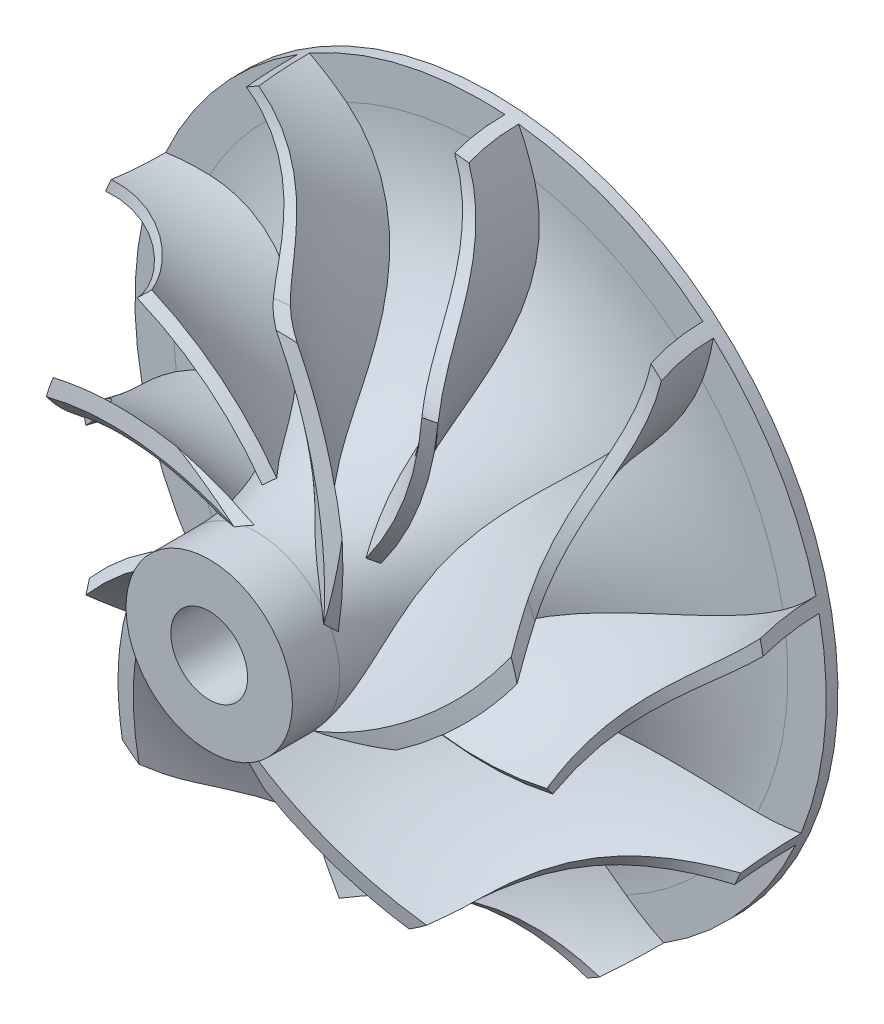
SolidWorks part; units mm, degrees
material "6061-T6 (SS)"
ref_plane "Front Plane" through (0, 0, 0) normal (0, 0, 1) x (1, 0, 0)
ref_plane "Top Plane" through (0, 0, 0) normal (0, 1, 0) x (1, 0, 0)
ref_plane "Right Plane" through (0, 0, 0) normal (1, 0, 0) x (0, 0, -1)
sketch "Sketch1" plane through (0, 0, 0) normal (1, 0, 0) x (0, 0, -1)
  line L0 (0, 0) -> (-24.5, 0) construction
  line L1 (-24.5, 3) -> (-24.5, 6.5)
  line L2 (0, 53.2891) -> (0, 0) construction
  line L3 (-24.5, 6.5) -> (-20.8, 6.5)
  line L4 (-24.5, 3) -> (0, 3)
  line L5 (0, 3) -> (0, 7)
  line L6 (-2.3876, 27) -> (-2.3876, 16.51)
  line L7 (-2.3876, 27) -> (-3.3, 27)
  line L8 (-3.3, 27) -> (-3.3, 24)
  arc A0 (-3.3, 24) -> (-20.8, 6.5) centre (-20.8, 24) cw
  arc A1 (0, 7) -> (-2.3876, 16.51) centre (17.7457, 16.51) cw
  dimension "D1" = 6
  dimension "D2" = 13
  dimension "D3" = 3.3
  dimension "D4" = 14
  dimension "D5" = 54
  dimension "D6" = 24.5
  dimension "D7" = 33.02
  dimension "D8" = 2.3876
  dimension "D9" = 48
revolve "Revolve1" add sketch "Sketch1" angle 360 about L0
sketch "Sketch2" plane through (0, 0, 0) normal (1, 0, 0) x (0, 0, -1)
  line L0 (0, 0) -> (-36.3996, 0) construction
  line L1 (-3.3, 24) -> (-3.3, -24) construction
  line L2 (-20.8, 6.5) -> (-20.8, -6.5) construction
  line L3 (-3.3, 27) -> (-3.3, -27) construction
  line L4 (-3.3, 4.5438) -> (-3.3, 5.4562)
  line L5 (-20.407, -5.2316) -> (-21.193, -4.7684)
  arc A0 (-3.3, 5) -> (-20.8, -5) centre (-3.3, -15.3125) ccw construction
  arc A1 (-3.3, 5.4562) -> (-21.193, -4.7684) centre (-3.3, -15.3125) ccw
  arc A2 (-3.3, 4.5438) -> (-20.407, -5.2316) centre (-3.3, -15.3125) ccw
  dimension "D1" = 5
  dimension "D2" = 5
  dimension "D3" = 0.4562
  dimension "D4" = 0.4562
sketch "Sketch3" plane through (0, 0, 0) normal (0, 0, 1) x (1, 0, 0)
  line L0 (0, 0) -> (40.1259, 0) construction
  line L1 (0, 0) -> (21.8435, 15.8702) construction
  arc A0 (0, 0) -> (22.9676, 22.9944) centre (0, 22.9676) ccw
  circle A2 centre (0, 0) radius 32.5 construction
  dimension "D2" = 65
  dimension "D3" = 22.9676
  dimension "D1" = 36
sweep "Sweep1" add profiles "Sketch2" path "Sketch3"
ref_axis "Axis1" through (0, 0, 24.5) along (0, 0, -1)
sketch "Sketch4" plane through (0, 0, 0) normal (1, 0, 0) x (0, 0, -1)
  line L0 (-20.8, -6.5) -> (-20.8, 6.5) construction
  line L1 (-3.3, 24) -> (-3.3, -24) construction
  line L2 (-24.5, 0) -> (0, 0) construction
  line L3 (-3.3, -5.4562) -> (-3.3, -4.5438)
  line L4 (-16.3269, 0.3268) -> (-16.9255, -0.3618)
  arc A0 (-20.8, 5) -> (-3.3, -5) centre (-3.3, 15.3125) ccw construction
  arc A1 (-16.9255, -0.3618) -> (-3.3, -5.4562) centre (-3.3, 15.3125) ccw
  arc A2 (-16.3269, 0.3268) -> (-3.3, -4.5438) centre (-3.3, 15.3125) ccw
  arc A4 (-21.193, 4.7684) -> (-3.3, -5.4562) centre (-3.3, 15.3125) ccw construction
  arc A5 (-20.407, 5.2316) -> (-3.3, -4.5438) centre (-3.3, 15.3125) ccw construction
  dimension "D1" = 5
  dimension "D2" = 5
  dimension "D5" = 41
  dimension "D3" = 0.4562
  dimension "D4" = 0.4562
sketch "Sketch5" plane through (0, 0, 0) normal (0, 0, 1) x (1, 0, 0)
  line L0 (0, 0) -> (-37.6758, 0) construction
  line L1 (-21.8435, -15.8702) -> (0, 0) construction
  arc A0 (0, 0) -> (-22.9676, -22.9944) centre (0, -22.9676) ccw
  arc A1 (17.3611, 20.6783) -> (18.1774, 19.9645) centre (0, 0) ccw construction
  circle A2 centre (0, 0) radius 32.5 construction
  dimension "D2" = 65
  dimension "D3" = 22.9676
  dimension "D1" = 36
sweep "Sweep2" add profiles "Sketch4" path "Sketch5"
pattern_circular "CirPattern2" count 5 over 360 about axis through (0, 0, 24.5) along (0, 0, -1) of "Sweep2", "Sweep1"
sketch "Sketch6" plane through (0, 0, 24.5) normal (0, 0, 1) x (1, 0, 0)
  circle A0 centre (0, 0) radius 3 construction
  circle A1 centre (0, 0) radius 3
extrude "Cut-Extrude1" cut sketch "Sketch6" against normal through all
sketch "Sketch7" plane through (0, 0, 0) normal (1, 0, 0) x (0, 0, -1)
  line L0 (0, 0) -> (-44.104, 0) construction
  line L1 (-21.193, 6.5) -> (-18.9855, 19.1)
  line L2 (-21.193, 22.9999) -> (-21.193, -4.3436) construction
  line L3 (-20.8, 6.5) -> (-24.5, 6.5) construction
  line L4 (-18.9855, 19.1) -> (-16.7325, 19.1)
  line L5 (-21.193, 6.5) -> (-21.193, 40)
  line L6 (-7.8, 27) -> (-3.3, 27)
  line L7 (-21.193, 40) -> (-3.3, 40)
  line L8 (-3.3, 40) -> (-3.3, 27)
  arc A0 (-16.7325, 19.1) -> (-7.8, 27) centre (-16.7325, 28.1) ccw
  dimension "D3" = 9
  dimension "D1" = 4.5
  dimension "D2" = 38.2
  dimension "D4" = 80
  dimension "D5" = 2.253
revolve "Cut-Revolve2" cut sketch "Sketch7" angle 360 about L0
